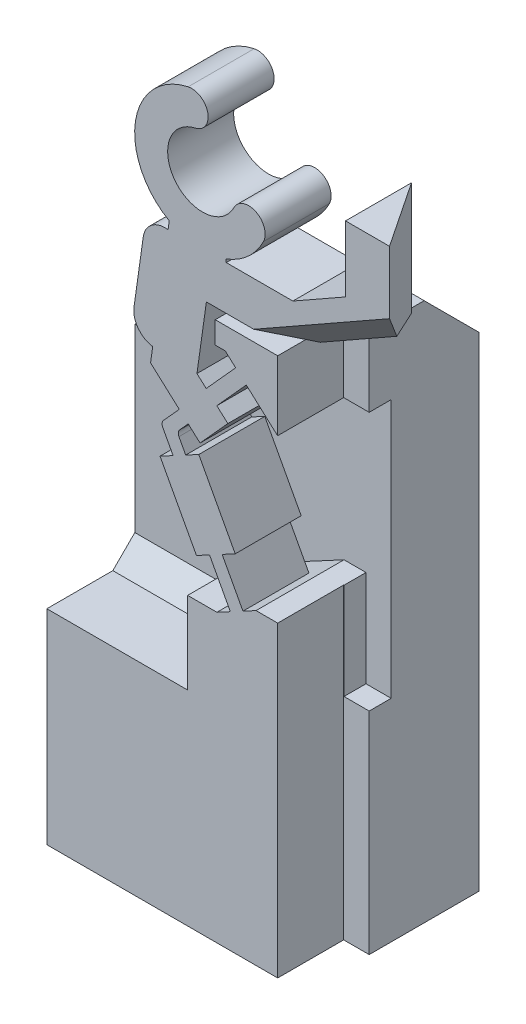
SolidWorks part; units mm, degrees
material "Nylon 6/12"
ref_plane "Front Plane" through (0, 0, 0) normal (0, 0, 1) x (1, 0, 0)
ref_plane "Top Plane" through (0, 0, 0) normal (0, 1, 0) x (1, 0, 0)
ref_plane "Right Plane" through (0, 0, 0) normal (1, 0, 0) x (0, 0, -1)
sketch "Sketch-SkeletonConfigUp" plane through (0, 0, 0) normal (0, 0, 1) x (1, 0, 0)
  line L0 (0, 0) -> (0, -50000) construction
  line L1 (0, 0) -> (4.5811, 6.2164) construction
  line L2 (9.8143, 13.3177) -> (4.5811, 13.945) construction
  line L3 (4.5811, 13.945) -> (1.9779, 11.0613) construction
  line L4 (1.9779, 11.0613) -> (4.5811, 6.2164) construction
  line L5 (4.5811, 13.945) -> (7.7356, 18.3956) construction
  line L6 (1.9779, 11.0613) -> (3.5045, 21.8722) construction
  line L7 (4.5811, 6.2164) -> (9.8143, 13.3177) construction
  line L8 (-587.3593, -797.0242) -> (9.8143, 13.3177) construction
  dimension "D2" = 7.7221
  dimension "D3" = 8.8212
  dimension "D4" = 5.2707
  dimension "D5" = 119.553
  dimension "D6" = 3.8848
  dimension "D7" = 5.4552
  dimension "D8" = 10.9181
  dimension "D9" = 5.5
  dimension "D10" = 6.745
  dimension "D11" = 145.964
  dimension "D12" = 143.612
  dimension "D13" = 8.038
sketch "Sketch-SkeletonConfigDown" plane through (0, 0, 0) normal (0, 0, 1) x (1, 0, 0)
  line L0 (0, 0) -> (0, -50000) construction
  line L1 (0, 0) -> (4.5811, 6.2164) construction
  line L2 (9.8143, 13.3177) -> (4.5811, 13.945) construction
  line L3 (4.5811, 13.945) -> (7.1843, 11.0614) construction
  line L4 (7.1843, 11.0614) -> (4.5811, 6.2164) construction
  line L5 (4.5811, 13.945) -> (0.4753, 17.5368) construction
  line L6 (7.1843, 11.0614) -> (-3.4146, 13.6822) construction
  line L7 (4.5811, 6.2164) -> (9.8143, 13.3177) construction
  line L8 (-589.9357, -800.5203) -> (9.8143, 13.3177) construction
  dimension "D2" = 7.7221
  dimension "D3" = 8.8212
  dimension "D4" = 5.2707
  dimension "D5" = 119.553
  dimension "D6" = 3.8848
  dimension "D7" = 5.4552
  dimension "D8" = 10.9181
  dimension "D9" = 5.5
  dimension "D10" = 6.745
  dimension "D11" = 145.964
  dimension "D1" = 143.612
  dimension "D12" = 76.111
ref_plane "Plane-Cam Base" through (12.592, 0, 0) normal (1, 0, 0) x (0, 0, -1)
ref_plane "Plane-Down-to-Up Derailleur Clearance" through (10.092, 0, 0) normal (1, 0, 0) x (0, 0, -1)
ref_plane "Plane-Cam Cavity Roof" through (8.592, 0, 0) normal (1, 0, 0) x (0, 0, -1)
sketch "Sketch-SwitchBossUp" plane through (0, 0, 0) normal (0, 0, 1) x (1, 0, 0)
  line L2 (10.0045, 20.1935) -> (10.0045, 23.1883)
  line L3 (10.0045, 23.1883) -> (12.0045, 23.1883)
  line L4 (12.0045, 23.1883) -> (12.0045, 19.1883)
  line L8 (1.9899, 19.1817) -> (1.937, 18.807)
  line L9 (1.9779, 11.0613) -> (3.5045, 21.8722) construction
  line L11 (2.8258, 4.3534) -> (2.8258, 1.1264)
  line L15 (2.1649, 10.0266) -> (2.7375, 10.3343) construction
  line L16 (1.9779, 11.0613) -> (4.5811, 6.2164) construction
  line L19 (3.6698, 13.4205) -> (4.1522, 12.9849) construction
  line L22 (5.0099, 14.905) -> (5.4924, 14.4695) construction
  line L23 (2.4447, 11.9871) -> (1.9057, 12.4737)
  line L32 (4.8674, 6.3703) -> (4.2948, 6.0626) construction
  line L40 (1.609, 11.0613) -> (2.3469, 11.0613) construction
  line L43 (2.874, 4.5093) -> (0.7934, 4.5093) construction
  line L51 (7.6103, 18.8344) -> (4.5811, 18.8344)
  line L66 (3.5045, 27.8193) -> (3.5045, 50027.8193) construction
  line L74 (0.3875, 14.9861) -> (0.807, 17.9566)
  line L75 (2.8258, 1.1264) -> (3.2603, 1.1264)
  line L81 (12.0045, 1033.6218) -> (12.0045, 19.1883) construction
  line L82 (3.9656, 18.869) -> (3.2498, 13.7996) construction
  line L84 (3.6783, 16.8344) -> (7.8579, 16.8344)
  line L88 (4.0801, 16.3344) -> (7.0567, 16.3344)
  line L92 (4.1604, 9.1122) -> (2.3986, 8.1656) construction
  line L93 (6.4487, 4.4471) -> (5.6239, 3.9968) construction
  line L95 (3.9656, 18.869) -> (3.6783, 16.8344) construction
  line L96 (3.822, 17.8517) -> (12.0045, 16.6962) construction
  line L97 (3.822, 17.8517) -> (2.9541, 17.9743) construction
  line L101 (2.4512, 10.1805) -> (1.9779, 11.0613) construction
  line L103 (3.5045, 21.8722) -> (5.6, 20.8363) construction
  line L107 (2.4447, 11.9871) -> (2.8513, 11.6201) construction
  line L109 (3.5045, 21.8722) -> (3.008, 24.1564) construction
  line L110 (12.0045, 19.1883) -> (7.8579, 16.8344)
  line L113 (2.8258, 4.8534) -> (2.8258, 4.3534)
  line L114 (3.3321, 10.6538) -> (2.7375, 10.3343)
  line L115 (7.0567, 16.3344) -> (13.3688, 16.3344)
  line L116 (13.3688, 16.3344) -> (13.3688, -1.1656)
  line L117 (13.3688, -1.1656) -> (5.2195, -1.1656)
  line L119 (10.4375, 13.1877) -> (10.4375, 2.56)
  line L121 (5.2195, -1.1656) -> (5.2195, 1.7741) construction
  line L122 (4.7682, 5.1817) -> (4.1572, 4.8534)
  line L123 (5.3407, 5.4894) -> (5.9353, 5.8088)
  line L124 (10.4375, 2.56) -> (9.304, 1.4266)
  line L125 (12.0045, 7.5844) -> (13.3688, 7.5844) construction
  line L127 (2.8513, 11.6201) -> (3.3903, 11.1335)
  line L130 (6.9353, 1.4266) -> (9.304, 1.4266)
  line L132 (2.8258, 4.3534) -> (3.6239, 3.9968) construction
  line L133 (4.3398, 14.1627) -> (4.8223, 13.7272) construction
  line L134 (3.3903, 11.1335) -> (4.6533, 12.5326)
  line L135 (4.1522, 12.9849) -> (4.6533, 12.5326)
  line L141 (4.2399, 1.6979) -> (3.2603, 1.1264) construction
  line L142 (3.2603, 1.1264) -> (3.2603, -1.1656)
  line L143 (12.0045, 19.1883) -> (12.0045, 16.6962) construction
  line L145 (12.0045, 16.6883) -> (12.0045, -49992.0368) construction
  line L149 (6.4487, 4.8534) -> (6.4487, 4.4471) construction
  line L150 (3.2603, -1.1656) -> (5.2195, -1.1656)
  line L151 (3.6239, 3.9968) -> (5.6239, 3.9968) construction
  line L152 (5.0099, 14.905) -> (3.6698, 13.4205)
  line L153 (5.4924, 14.4695) -> (4.1522, 12.9849)
  line L169 (3.8215, 6.9435) -> (4.7682, 5.1817)
  line L170 (5.3407, 5.4894) -> (4.3941, 7.2512)
  line L177 (4.3941, 7.2512) -> (3.8215, 6.9435) construction
  line L180 (5.9353, 5.8088) -> (6.4487, 4.8534) construction
  line L181 (4.1572, 4.8534) -> (2.8258, 4.8534)
  line L184 (4.1572, 4.8534) -> (6.4487, 4.8534) construction
  line L186 (4.5811, 18.8344) -> (4.5811, 18.9785)
  line L191 (2.1649, 10.0266) -> (1.5703, 9.7071)
  line L197 (3.5802, 7.2175) -> (3.5802, 7.3858) construction
  line L201 (2.8258, 4.3534) -> (2.8258, 3.9968) construction
  line L202 (2.8258, 3.9968) -> (3.6239, 3.9968) construction
  line L204 (5.2195, 1.4968) -> (3.2603, 1.4968) construction
  line L205 (3.2603, 1.4968) -> (3.2603, 1.1264) construction
  line L206 (5.2195, 1.7741) -> (6.299, 1.4266) construction
  line L207 (12.0045, 16.6962) -> (12.0045, 16.6883) construction
  line L208 (5.9353, 5.8088) -> (6.9353, 5.8088)
  line L209 (12.0045, 19.1883) -> (12.0045, 16.6883) construction
  line L210 (10.0045, 20.1935) -> (7.6103, 18.8344)
  line L211 (5.2195, 1.7741) -> (4.6239, 3.9968) construction
  line L212 (4.2399, 1.6979) -> (3.6239, 3.9968) construction
  line L213 (5.6239, 3.9968) -> (4.6239, 3.9968) construction
  line L215 (4.5343, 15.3344) -> (4.0801, 15.3344)
  line L217 (3.6698, 13.4205) -> (3.2498, 13.7996)
  line L218 (4.3941, 7.2512) -> (4.9887, 7.5706)
  line L219 (6.9353, 5.8088) -> (6.9353, 1.4266)
  line L225 (3.2498, 13.7996) -> (3.6783, 16.8344)
  line L226 (4.0801, 15.3344) -> (4.0801, 16.3344)
  line L235 (1.937, 18.807) -> (1.1403, 13.1647) construction
  line L236 (1.5703, 9.7071) -> (3.2269, 6.624)
  line L237 (1.1403, 13.1647) -> (1.2379, 13.8561)
  line L241 (1.9779, 11.0613) -> (2.648, 11.8036) construction
  line L242 (6.299, 1.4266) -> (6.9353, 1.4266) construction
  line L243 (2.7375, 10.3343) -> (2.4302, 10.9062)
  line L244 (2.4649, 11.1921) -> (2.8513, 11.6201)
  line L245 (2.1649, 10.0266) -> (1.6923, 10.9062)
  line L246 (1.727, 11.1921) -> (2.4447, 11.9871)
  line L247 (3.3321, 10.6538) -> (4.9887, 7.5706)
  line L248 (4.7682, 5.1817) -> (5.3407, 5.4894) construction
  line L249 (3.8215, 6.9435) -> (3.2269, 6.624)
  line L250 (1.9057, 12.4737) -> (3.1687, 13.8728) construction
  line L251 (4.5811, 13.945) -> (1.9779, 11.0613) construction
  line L252 (2.5372, 13.1732) -> (4.0218, 11.8331) construction
  line L253 (3.1687, 13.8728) -> (3.2498, 13.7996) construction
  line L254 (1.9057, 12.4737) -> (1.1403, 13.1647)
  line L255 (5.0099, 14.905) -> (4.5343, 15.3344)
  line L256 (5.4924, 14.4695) -> (6.9123, 13.1877)
  line L257 (6.9123, 13.1877) -> (10.4375, 13.1877)
  arc A0 (4.5811, 18.9785) -> (6.2723, 20.5039) centre (3.5045, 21.8722) ccw
  arc A1 (1.9899, 19.1817) -> (2.8487, 24.8892) centre (3.5045, 21.8722) cw
  arc A2 (2.8487, 24.8892) -> (3.1673, 23.4235) centre (3.008, 24.1564) cw
  arc A3 (6.2723, 20.5039) -> (4.9276, 21.1687) centre (5.6, 20.8363) ccw
  arc A4 (3.1673, 23.4235) -> (4.9276, 21.1687) centre (3.5045, 21.8722) ccw
  arc A19 (0.807, 17.9566) -> (1.937, 18.807) centre (1.7972, 17.8168) cw
  circle A28 centre (3.5045, 21.8722) radius 2.3375 construction
  arc A30 (0.3875, 14.9861) -> (1.2379, 13.8561) centre (1.3777, 14.8463) ccw
  arc A31 (2.4302, 10.9062) -> (2.4649, 11.1921) centre (2.6504, 11.0245) cw
  arc A32 (1.6923, 10.9062) -> (1.727, 11.1921) centre (1.9126, 11.0245) cw
  point P6 (3.2795, 8.6389)
  point P45 (3.2795, 12.5032)
  point P66 (4.5811, 6.2164)
  point P165 (4.5811, 13.945)
  dimension "D23" = 1.5875
  dimension "D24" = 0.75
  dimension "D21" = 0.25
  dimension "D7" = 2
  dimension "D11" = 8.5
  dimension "D17" = 0.5
  dimension "D9" = 17.5
  dimension "D22" = 1
  dimension "D15" = 45
  dimension "D44" = 2
  dimension "D46" = 2.5
  dimension "D47" = 4
  dimension "D10" = 15
  dimension "D12" = 2.5
  dimension "D19" = 1
  dimension "D8" = 0.65
  dimension "D27" = 0.65
  dimension "D6" = 0.65
  dimension "D25" = 2
  dimension "D26" = 2
  dimension "D5" = 1
  dimension "D16" = 2
  dimension "D28" = 2
  dimension "D18" = 1
  dimension "D20" = 0
  dimension "D14" = 0.5
  dimension "D29" = 2
  dimension "D30" = 1
  dimension "D31" = 5
  dimension "D32" = 1
extrude "Boss-Switch Body" add sketch "Sketch-SwitchBossUp" along normal blind 3
sketch "Sketch1" plane through (0, 0, 0) normal (0, 0, -1) x (-1, 0, 0)
  line L0 (-6.9353, 5.8088) -> (-5.9353, 5.8088)
  line L1 (-8.0801, -1.1656) -> (0.4122, -1.1656)
  line L2 (-8.0801, -1.1656) -> (-8.0801, 1.4266)
  line L4 (0.4122, -1.1656) -> (0.4122, 1.1264)
  line L5 (-4.0801, 13.1877) -> (-8.0801, 13.1877)
  line L10 (-8.0801, 13.1877) -> (-8.0801, 16.3344)
  line L11 (-4.2399, 1.6979) -> (-5.2399, 1.6979) construction
  line L12 (-8.0801, 16.3344) -> (-4.0801, 16.3344)
  line L13 (-4.2399, 1.6979) -> (-3.2603, 1.1264) construction
  line L14 (-4.0801, 16.3344) -> (-4.0801, 13.1877)
  line L22 (-3.2603, -1.1656) -> (-13.3688, -1.1656) construction
  line L23 (-2.8258, 1.1264) -> (0.4122, 1.1264)
  line L24 (-5.2399, 1.6979) -> (-6.299, 1.4266) construction
  line L25 (-6.9353, 1.4266) -> (-8.0801, 1.4266)
  line L26 (-10.4375, 13.1877) -> (-6.9123, 13.1877) construction
  line L27 (-5.9353, 5.8088) -> (-4.1572, 4.8534)
  line L28 (-4.1572, 4.8534) -> (-2.8258, 4.8534)
  line L29 (-2.8258, 4.8534) -> (-2.8258, 1.1264)
  line L30 (-6.9353, 5.8088) -> (-6.9353, 1.4266)
  line L31 (-6.299, 1.4266) -> (-6.9353, 1.4266) construction
  line L32 (-3.2603, 1.1264) -> (-2.8258, 1.1264) construction
  dimension "D4" = 4
extrude "Boss-Flange Width" add sketch "Sketch1" along normal blind 5
ref_plane "Plane-Sta2Sit Groove" through (3.5045, 0, 0) normal (1, 0, 0) x (0, 0, -1)
ref_plane "Plane-Cam Outer Surface" through (-8.5755, 0, 0) normal (1, 0, 0) x (0, 0, -1)
ref_plane "Plane-FlangeTop" through (-3.5755, 0, 0) normal (1, 0, 0) x (0, 0, -1)
sketch "Sketch2" plane through (-3.5755, 0, 0) normal (1, 0, 0) x (0, 0, -1)
  line L0 (5, 16.3344) -> (-3, 16.3344) construction
  line L1 (5, 13.1877) -> (1, 13.1877)
  line L2 (5, 13.1877) -> (5, 16.3344)
  line L3 (5, 16.3344) -> (1, 16.3344)
  line L4 (1, 13.1877) -> (1, 16.3344)
  line L5 (5, 13.1877) -> (0, 13.1877) construction
  line L10 (-3, -1.1656) -> (-3, 16.3344) construction
  line L11 (5, 1.1264) -> (-3, 1.1264)
  line L12 (5, 1.1264) -> (5, -1.1656)
  line L13 (5, -1.1656) -> (-3, -1.1656)
  line L14 (-3, 1.1264) -> (-3, -1.1656)
  line L15 (0, 11.0613) -> (0, 21.8722) construction
  line L16 (5, 1.1264) -> (0, 1.1264) construction
  line L17 (5, 1.4266) -> (5, -1.1656) construction
  dimension "D1" = 1
extrude "Boss-Flange Height" add sketch "Sketch2" along normal up to surface (8.2034 mm away)
sketch "Sketch17" plane through (0, 1.1264, 0) normal (0, -1, 0) x (1, 0, 0)
  line L0 (8.0801, -5) -> (-3.5755, -5)
  line L1 (8.0801, -5) -> (-3.5755, -5) construction
  line L2 (-3.5755, -5) -> (-3.5755, -1)
  line L3 (-3.5755, -1) -> (8.0801, -1)
  line L4 (8.0801, -1) -> (8.0801, -5)
  line L5 (-3.5755, -1) -> (-3.5755, -5) construction
  line L6 (8.0801, -5) -> (8.0801, 0) construction
  line L7 (4.0801, -1) -> (-3.5755, -1) construction
extrude "Boss-Flange Support" add sketch "Sketch17" against normal up to surface (12.0613 mm away) up to face at (5.1095, 13.1877, -0.5455)
sketch "Sketch27" plane through (0, 0, 0) normal (0, 0, 1) x (1, 0, 0)
  line L0 (4.0801, 15.3344) -> (4.5343, 15.3344)
  line L1 (4.5343, 15.3344) -> (6.9123, 13.1877)
  line L2 (6.9123, 13.1877) -> (4.0801, 13.1877)
  line L3 (4.0801, 13.1877) -> (8.0801, 13.1877) construction
  line L4 (4.0801, 13.1877) -> (4.0801, 16.3344) construction
  line L5 (4.0801, 13.1877) -> (4.0801, 15.3344)
extrude "Cut-Wall Gap" cut sketch "Sketch27" against normal up to surface (1 mm away) up to face at (3.8987, 7.1229, -1)
sketch "Sketch26" plane through (0, 0, -1) normal (0, 0, 1) x (1, 0, 0)
  line L0 (4.0801, 16.3344) -> (-3.5755, 16.3344)
  line L1 (-3.5755, 16.3344) -> (-3.5755, 10.3344)
  line L2 (-3.5755, 16.3344) -> (-3.5755, 1.1264) construction
  line L3 (-3.5755, 10.3344) -> (4.0801, 10.3344)
  line L4 (4.0801, 10.3344) -> (4.0801, 16.3344)
  dimension "D1" = 6
extrude "Cut-Cam Slope Clearance" cut sketch "Sketch26" against normal through all
ref_plane "Plane-Tap Depth" through (0, 5.3344, 0) normal (0, 1, 0) x (1, 0, 0)
sketch "Sketch-HolePositions" plane through (0, -1.1656, 0) normal (0, -1, 0) x (1, 0, 0)
  line L0 (-3.5755, -3) -> (8.0801, -3) construction
  line L1 (8.0801, -5) -> (-3.5755, -5) construction
  line L2 (8.0801, -5) -> (8.0801, 0) construction
  line L4 (-3.5755, -22.2167) -> (-3.5755, 22.2167) construction
  point P6 (-0.5755, -3)
  point P7 (5.5801, -3)
  dimension "D1" = 3
  dimension "D2" = 2.5
  dimension "D3" = 2
sketch "Sketch6" plane through (0, -1.1656, 0) normal (0, -1, 0) x (-1, 0, 0)
  point P0 (0.5755, 3)
  point P3 (-5.5801, 3)
hole_wizard "Tap Drill for M2x0.4 Tap1" positions "Sketch6" profile "Sketch5" hole size "M2x0.4" standard "ANSI Metric" end condition through all
sketch "Sketch5" plane through (-0.5755, -1.1656, -3) normal (1, 0, 0) x (0, 0, -1)
  line L0 (0, 0) -> (0, 26.0719)
  line L1 (0, 26.0719) -> (0.8, 26.0719)
  line L2 (0.8, 26.0719) -> (0.8, 0)
  line L5 (0.8, 0) -> (0, 0)
  line L11 (0, -6.35) -> (0, 107.95) construction
  dimension "Thru Hole Dia." = 1.6
  dimension "Thru Hole Depth" = 26.0719
sketch "Sketch9" plane through (0, -1.1656, 0) normal (0, -1, 0) x (1, 0, 0)
  point P0 (-0.5755, -3)
  point P3 (5.5801, -3)
hole_wizard "M2 Clearance Hole2" positions "Sketch9" profile "Sketch8" hole size "M2" standard "ANSI Metric"
sketch "Sketch8" plane through (-0.5755, -1.1656, -3) normal (1, 0, 0) x (0, 0, -1)
  line L0 (0, 0) -> (0, 7.221)
  line L1 (0, 7.221) -> (1.2, 6.5)
  line L2 (1.2, 6.5) -> (1.2, 0)
  line L5 (1.2, 0) -> (0, 0)
  line L10 (0, 7.221) -> (-1.2, 6.5) construction
  line L11 (0, -6.35) -> (0, 107.95) construction
  dimension "Hole Dia." = 2.4
  dimension "Hole Depth" = 6.5
  dimension "Drill Angle" = 118
sketch "Sketch-Measurements for Derailleur Ramps" [suppressed] plane through (0, 0, 0) normal (0, 0, 1) x (1, 0, 0)
  line L0 (2.8784, 16.9852) -> (4.2265, 19.8331)
  line L1 (3.5524, 18.4092) -> (3.0492, 18.6474)
  line L2 (1.9779, 11.0613) -> (4.4465, 28.5428) construction
  line L3 (3.0492, 18.6474) -> (-4.0642, 13.8428)
  line L4 (7.1843, 11.0614) -> (-9.9544, 15.2993) construction
  line L5 (3.0492, 18.6474) -> (2.1536, 12.3053)
  line L6 (2.1536, 12.3053) -> (-4.0642, 13.8428)
  line L7 (-0.5075, 16.2451) -> (-0.5075, 18.6474)
  line L8 (-0.5075, 18.6474) -> (3.0492, 18.6474)
  line L9 (7.1843, 11.0614) -> (1.9779, 11.0613)
  line L10 (5.8827, 8.6389) -> (3.2795, 8.6389)
  line L12 (7.1843, 11.0614) -> (4.5811, 6.2164) construction
  line L13 (4.5811, 8.6389) -> (4.5811, 8.7912)
  line L14 (4.5811, 6.2164) -> (5.8827, 8.6389)
  line L15 (1.9779, 11.0613) -> (4.5811, 6.2164) construction
  line L16 (3.2795, 8.6389) -> (4.5811, 6.2164)
  line L17 (5.8827, 8.6389) -> (5.8827, 8.7912)
  dimension "D1" = 3.5567
  dimension "D2" = 1.3016
sketch "Sketch12" plane through (0, 23.1883, 0) normal (0, 1, 0) x (1, 0, 0)
  line L0 (10.0045, 0) -> (12.0045, -3)
  line L1 (12.0045, -3) -> (12.0045, 0)
  line L2 (12.0045, 0) -> (10.0045, 0)
extrude "Cut-Up-to-Down Cantilever Slope" cut sketch "Sketch12" against normal up to next
ref_plane "Plane1" [suppressed] through (0, 6.9404, 0) normal (0, 1, 0) x (1, 0, 0)
sketch "Sketch-Derailleur Location" [suppressed] plane through (0, 6.9404, 0) normal (0, 1, 0) x (1, 0, 0)
  line L0 (12.9465, 0) -> (12.9465, -3)
  line L1 (4.2399, -3) -> (3.2603, -3) construction
  line L2 (-119237.4187, 0) -> (9.8143, 0) construction
  point P0 (12.9465, 0)
  point P8 (12.9465, -1.5)
ref_plane "Plane-Cantilever Cut" [suppressed] through (7.0848, 8.5204, -1.9058) normal (-0.6301, -0.7578, 0.1695) x (-0.7765, 0.6151, -0.1368)
sketch "Sketch14" [suppressed] plane through (7.0848, 8.5204, -1.9058) normal (-0.6301, -0.7578, 0.1695) x (-0.7765, 0.6151, -0.1368)
  line L0 (2.3023, -1.6911) -> (-0.3551, -1.6911)
  line L2 (2.3023, -4.3362) -> (2.3023, -1.6911)
  line L3 (-0.3551, -1.6911) -> (-0.3551, -4.4608)
  line L5 (-0.3551, -4.4608) -> (1.0087, -5.0843)
  line L6 (1.0087, -5.0843) -> (2.3023, -4.3362)
extrude "Cut-Down-to-Up Cantilever Slope" [suppressed] cut sketch "Sketch14" against normal up to next
ref_plane "Plane-Symmetry Plane" through (0, 0, 1.5) normal (0, 0, 1) x (1, 0, 0)
sketch "Sketch-Cable Center Point" plane through (0, 0, 1.5) normal (0, 0, 1) x (1, 0, 0)
  line L0 (3.5045, 21.8722) -> (3.3935, 21.0862)
  line L1 (1.9779, 11.0613) -> (3.5045, 21.8722) construction
  point P0 (3.5045, 21.8722)
  dimension "D1" = 0.7937
chamfer "Chamfer-Flange Support" [suppressed] distance 1.5 angle 45
chamfer "Chamfer-Flange Support 3" distance 1 angle 45 1 edges at (-0.3748, 1.1264, -1)
chamfer "Chamfer7" distance 1 angle 45 1 edges at (9.9312, 18.0113, 3)
sketch "Sketch25" plane through (0, 0, 3) normal (0, 0, 1) x (1, 0, 0)
  line L0 (13.3688, 16.3344) -> (13.3688, -1.1656)
  line L1 (13.3688, -1.1656) -> (6.9204, -1.1656)
  line L2 (-3.5755, -1.1656) -> (13.3688, -1.1656) construction
  line L3 (6.9204, -1.1656) -> (6.9204, 16.3344)
  line L4 (13.3688, 16.3344) -> (4.0801, 16.3344) construction
  line L5 (6.9204, 16.3344) -> (13.3688, 16.3344)
extrude "Cut-Base Removal" cut sketch "Sketch25" against normal up to surface (3 mm away) up to face at (9.9152, 6.9029, 0)
chamfer "Chamfer8" distance 2.5 angle 45 1 edges at (6.0801, 16.3344, -5)
sketch "Sketch28" plane through (0, -1.1656, 0) normal (0, -1, 0) x (1, 0, 0)
  line L0 (-3.5755, 3) -> (6.9204, 3)
  line L1 (6.9204, 3) -> (6.9204, 0)
  line L2 (6.9204, 0) -> (8.0801, 0)
  line L3 (8.0801, 0) -> (8.0801, -5)
  line L4 (8.0801, -5) -> (-3.5755, -5)
  line L5 (-3.5755, -5) -> (-3.5755, 3)
  circle A0 centre (5.5801, -3) radius 1.2 construction
  circle A1 centre (-0.5755, -3) radius 1.2 construction
  circle A2 centre (5.5801, -3) radius 1.2
  circle A3 centre (-0.5755, -3) radius 1.2
extrude "Boss-Rear Fill" add sketch "Sketch28" along normal blind 7
equation "\"axle-diameter\"=2"
equation "\"switch-thickness\"=12"
equation "\"base-width\"=4.0"
equation "\"axle-bushing-radius\"=3"
equation "\"clearance\"= 0.25"
equation "\"arm-width\"=1.5"
equation "\"min-diameter\"=70"
equation "\"alpha\"=143.6120"
equation "\"gamma\"=119.5526"
equation "\"delta\"=145.9637"
equation "\"epsilon\"=6.7452"
equation "\"l_AB\"=8.8212"
equation "\"l_AC\"=4.4914"
equation "\"l_BD\"=5.2707"
equation "\"l_CD\"=3.8848"
equation "\"l_CE\"=10.9181"
equation "\"l_DF\"=5.4552"
equation "\"l_OA\"=7.7221"
equation "\"D2@Sketch-SkeletonConfigUp\" = \"l_OA\""
equation "\"D3@Sketch-SkeletonConfigUp\" = \"l_AB\""
equation "\"D4@Sketch-SkeletonConfigUp\" = \"l_BD\""
equation "\"D5@Sketch-SkeletonConfigUp\" = \"gamma\""
equation "\"D6@Sketch-SkeletonConfigUp\" = \"l_CD\""
equation "\"D7@Sketch-SkeletonConfigUp\" = \"l_DF\""
equation "\"D8@Sketch-SkeletonConfigUp\" = \"l_CE\""
equation "\"D_groove\"=3.175"
equation "\"D7@Sketch-SkeletonConfigDown\" = \"l_DF\""
equation "\"D6@Sketch-SkeletonConfigDown\" = \"l_CD\""
equation "\"D2@Sketch-SkeletonConfigDown\" = \"l_OA\""
equation "\"D3@Sketch-SkeletonConfigDown\" = \"l_AB\""
equation "\"D9@Sketch-SkeletonConfigDown\"=5.5"
equation "\"D8@Sketch-SkeletonConfigDown\" = \"l_CE\""
equation "\"D5@Sketch-SkeletonConfigDown\" = \"gamma\""
equation "\"D4@Sketch-SkeletonConfigDown\" = \"l_BD\""
equation "\"D1@Sketch-SkeletonConfigDown\" = \"alpha\""
equation "\"hinge_length\"=1.5"
equation "\"hinge_depth\"=0.25"
equation "\"D10@Sketch-SkeletonConfigUp\"=\"epsilon\""
equation "\"D11@Sketch-SkeletonConfigUp\"=\"delta\""
equation "\"D12@Sketch-SkeletonConfigUp\"=\"alpha\""
equation "\"D11@Sketch-SkeletonConfigDown\"=\"delta\""
equation "\"D10@Sketch-SkeletonConfigDown\"=\"epsilon\""
equation "\"EE_dx\"=8.9056"
equation "\"EE_dy\"=8.1898"
equation "\"r_groove\"=\"D_groove\"/2"
equation "\"t_wall\"=25.4/16"
equation "\"width_lower\"=\"D_groove\"+\"t_wall\""
equation "\"cable_to_bottom\"=30.6257"
equation "\"switch_EE-up_base_dy\"=24"
equation "\"switch_EE-down_base_dy\"=16"
equation "\"D_axle\"=25.4/8"
equation "\"D_up_to_down\"=16"
equation "\"D_down_to_up\"=25"
equation "\"t_cam_base\"=7.5"
equation "\"D23@Sketch-SwitchBossUp\"=\"D_groove\"/2"
equation "\"D1@Sketch-Cable Center Point\"=\"D_groove\"/4"
